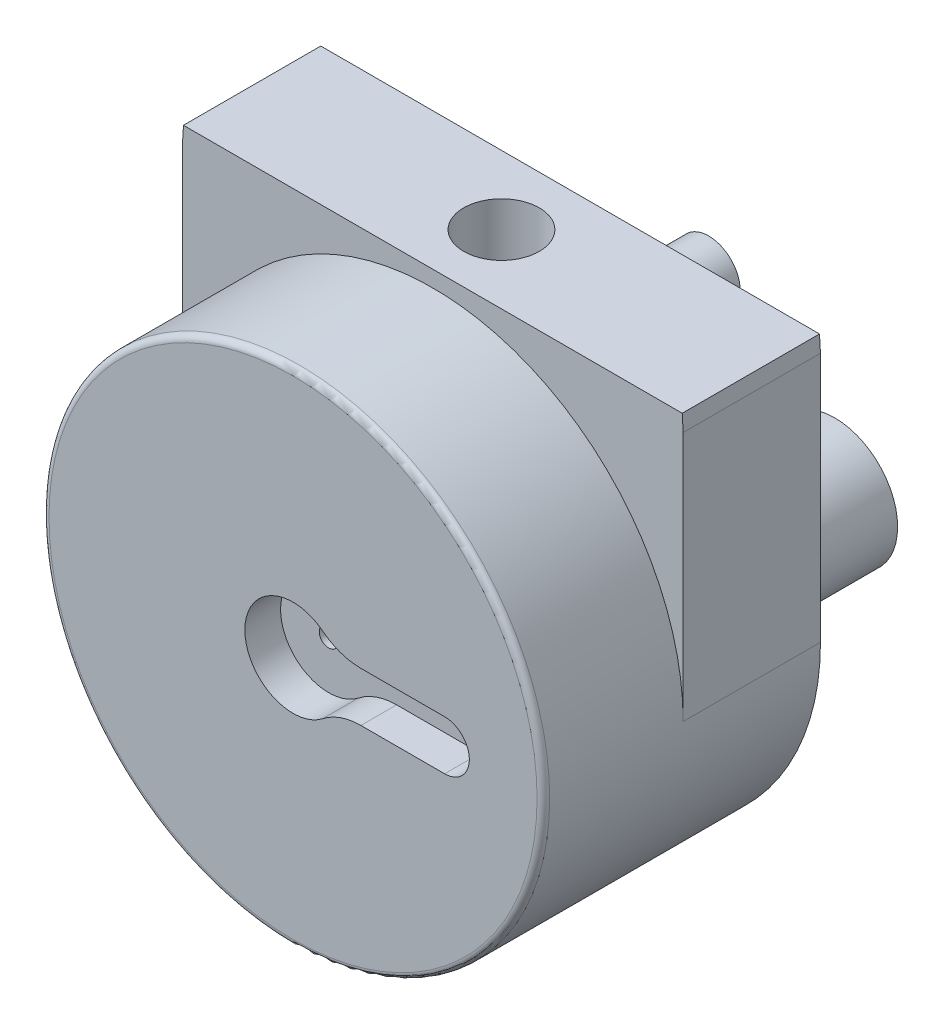
SolidWorks part; units mm, degrees
material "6061 Alloy"
ref_plane "Front Plane" through (0, 0, 0) normal (0, 0, 1) x (1, 0, 0)
ref_plane "Top Plane" through (0, 0, 0) normal (0, 1, 0) x (1, 0, 0)
ref_plane "Right Plane" through (0, 0, 0) normal (1, 0, 0) x (0, 0, -1)
sketch "Sketch1" plane through (0, 0, 0) normal (0, 0, 1) x (1, 0, 0)
  circle A0 centre (0, 0) radius 39.75
  dimension "D1" = 79.5
extrude "Boss-Extrude1" add sketch "Sketch1" along normal blind 44
sketch "Sketch2" plane through (0, 0, 0) normal (0, 1, 0) x (1, 0, 0)
  line L0 (39.75, -44) -> (39.75, 0) construction
  line L1 (-39.75, 0) -> (39.75, 0)
  line L2 (-39.75, 0) -> (-39.75, -21.8)
  line L3 (-39.75, -21.8) -> (39.75, -21.8)
  line L4 (39.75, 0) -> (39.75, -21.8)
  dimension "D1" = 21.8
extrude "Boss-Extrude2" add sketch "Sketch2" along normal through all
sketch "Sketch3" plane through (0, 0, 0) normal (0, 0, -1) x (-1, 0, 0)
  line L0 (0, 0) -> (0, 203.2) construction
  line L1 (-39.75, 39.75) -> (-29.9473, 204.9767)
  line L2 (39.75, 39.75) -> (29.9473, 204.9767)
  line L3 (39.75, 39.75) -> (39.75, 0) construction
  line L4 (-39.75, 39.75) -> (39.75, 39.75) construction
  circle A0 centre (0, 203.2) radius 30
  line M5 (39.75, 39.75) -> (-39.75, 39.75)
  dimension "D1" = 60
  dimension "D2" = 203.2
extrude "Boss-Extrude3" add sketch "Sketch3" against normal up to surface (21.8 mm away) contours L0 A0 L1 M5 | L0 L2 A0 M5 | A0 region at (18.2462, 107.3979, 0) region at (-18.2462, 107.3979, 0) region at (21.2148, 183.2065, 0) up to face at (29.2442, 29.2442, 21.8)
ref_plane "Plane7" through (0, 233.2, 0) normal (0, 1, 0) x (1, 0, 0)
sketch "Sketch5" plane through (0, 0, 21.8) normal (0, 0, 1) x (1, 0, 0)
  line L0 (10.25, 179.4146) -> (10.25, 171.95)
  line L1 (10.25, 171.95) -> (-10.25, 171.95)
  line L2 (-10.25, 171.95) -> (-10.25, 179.4146)
  circle A0 centre (0, 203.2) radius 25.9
  dimension "D1" = 20.5
  dimension "D4" = 51.8
  dimension "D6" = 7.4646
  dimension "D7" = 7.4646
extrude "Cut-Extrude2" cut sketch "Sketch5" against normal up to next contours A0 region at (0, 203.2, 21.8)
extrude "Cut-Extrude3" cut sketch "Sketch5<3>" against normal blind 10.25 contours A0 L2 L1 L0 region at (0, 175.0039, 21.8)
sketch "Sketch5<3>" plane through (0, 0, 21.8) normal (0, 0, 1) x (1, 0, 0) same geometry as "Sketch5"
sketch "Sketch7" plane through (0, 0, 21.8) normal (0, 0, 1) x (1, 0, 0)
  line L0 (-10.25, 171.95) -> (-10.25, 179.4146) construction
  line L1 (10.25, 171.95) -> (-12.25, 171.95)
  line L2 (10.25, 171.95) -> (10.25, 169.95)
  line L3 (10.25, 169.95) -> (-12.25, 169.95)
  line L4 (-12.25, 171.95) -> (-12.25, 169.95)
  line L6 (10.25, 169.95) -> (12.25, 169.95)
  line L7 (10.25, 169.95) -> (10.25, 212.2)
  line L8 (10.25, 212.2) -> (12.25, 212.2)
  line L9 (12.25, 169.95) -> (12.25, 212.2)
  line L10 (-12.25, 212.2) -> (-28.6182, 212.2)
  line L11 (-10.25, 171.95) -> (-12.25, 171.95)
  line L12 (-10.25, 171.95) -> (-10.25, 212.2)
  line L13 (-10.25, 212.2) -> (-12.25, 212.2)
  line L14 (-12.25, 171.95) -> (-12.25, 212.2)
  line L15 (-12.25, 210.2) -> (-29.1719, 210.2)
  line L16 (12.25, 212.2) -> (28.6182, 212.2)
  line L17 (12.25, 210.2) -> (29.1719, 210.2)
  line L18 (0, 203.2) -> (0, 212.2) construction
  line L19 (-10.25, 212.2) -> (10.25, 212.2) construction
  arc A0 (29.9473, 204.9767) -> (-29.9473, 204.9767) centre (0, 203.2) ccw construction
  arc A1 (-28.6182, 212.2) -> (-29.1719, 210.2) centre (0, 203.2) ccw
  arc A2 (29.1719, 210.2) -> (28.6182, 212.2) centre (0, 203.2) ccw
  arc M13 (29.9473, 204.9767) -> (-29.9473, 204.9767) centre (0, 203.2) ccw
  line M15 (10.25, 179.4146) -> (10.25, 171.95)
  line M16 (10.25, 171.95) -> (-10.25, 171.95)
  line M17 (-10.25, 171.95) -> (-10.25, 179.4146)
  arc M18 (-10.25, 179.4146) -> (10.25, 179.4146) centre (0, 203.2) cw
  dimension "D9" = 30
  dimension "D1" = 2
  dimension "D2" = 2
  dimension "D3" = 2
  dimension "D4" = 2
  dimension "D5" = 2
  dimension "D6" = 2
  dimension "D7" = 9
  dimension "D8" = 42.25
extrude "Boss-Extrude5" add sketch "Sketch7" along normal blind 31 contours L15 L14 L10 M18 | L15 L10 M18 M13 | L14 L12 L13 M18 | L14 L1 M17 M18 | L1 L4 L3 L2 M16 | L6 L9 L2 M18 M15 | L9 L8 L7 M18 | L9 L17 L16 M18 | L17 L16 M18 M13 region at (-1, 170.95, 21.8) region at (11.2662, 174.9188, 21.8) region at (-11.2703, 175.9197, 21.8) region at (11.245, 196.0386, 21.8) region at (-11.245, 196.0386, 21.8) region at (18.4394, 211.1912, 21.8) region at (26.7656, 211.2037, 21.8) region at (-18.4394, 211.1912, 21.8) region at (-26.7656, 211.2037, 21.8)
sketch "Sketch8" plane through (0, 212.2, 0) normal (0, 1, 0) x (1, 0, 0)
  line L0 (-29.1719, -23.4904) -> (-12.25, -52.8)
  line L1 (29.1719, -52.8) -> (29.1719, -21.8) construction
  line L2 (12.25, -52.8) -> (29.1719, -23.4904)
  line L4 (-29.1719, -52.8) -> (-29.1719, -21.8) construction
  line L6 (-29.1719, -23.4904) -> (-29.1719, -52.8)
  line L7 (-29.1719, -52.8) -> (-12.25, -52.8)
  line L8 (12.25, -52.8) -> (29.1719, -52.8)
  line L9 (29.1719, -52.8) -> (29.1719, -23.4904)
  line L11 (29.1719, -52.8) -> (29.1719, -21.8) construction
  dimension "D1" = 2
  dimension "D2" = 30
  dimension "D3" = 2
  dimension "D4" = 30
extrude "Cut-Extrude4" cut sketch "Sketch8" against normal blind 10
sketch "Sketch9" plane through (0, 0, 52.8) normal (0, 0, 1) x (1, 0, 0)
  line L0 (-12.25, 169.95) -> (-12.25, 180.3801) construction
  line L1 (-12.25, 169.95) -> (12.25, 169.95)
  line L2 (-12.25, 169.95) -> (-12.25, 212.2)
  line L3 (-12.25, 212.2) -> (12.25, 212.2)
  line L4 (12.25, 169.95) -> (12.25, 212.2)
  line L5 (-12.25, 169.95) -> (-12.25, 210.2) construction
  line L6 (-12.25, 169.95) -> (-7.5, 174.7) construction
  line L7 (-7.5, 174.7) -> (-7.5, 189.7) construction
  line L8 (-7.5, 189.7) -> (-8, 210.2) construction
  line L9 (-8, 210.2) -> (0, 203.2) construction
  line L10 (0, 203.2) -> (8, 210.2) construction
  line L11 (8, 210.2) -> (7.5, 189.7) construction
  line L12 (7.5, 189.7) -> (7.5, 174.7) construction
  line L13 (7.5, 174.7) -> (12.25, 169.95) construction
  circle A0 centre (0, 203.2) radius 7.5
  circle A1 centre (-8, 210.2) radius 0.75
  circle A2 centre (8, 210.2) radius 0.75
  circle A3 centre (7.5, 189.7) radius 0.75
  circle A4 centre (7.5, 174.7) radius 0.75
  circle A5 centre (-7.5, 174.7) radius 0.75
  circle A6 centre (-7.5, 189.7) radius 0.75
  line M25 (12.25, 210.2) -> (12.25, 212.2)
  line M26 (12.25, 212.2) -> (10.25, 212.2)
  line M27 (10.25, 212.2) -> (10.25, 171.95)
  line M28 (10.25, 171.95) -> (-10.25, 171.95)
  line M29 (-10.25, 171.95) -> (-10.25, 212.2)
  line M30 (-10.25, 212.2) -> (-12.25, 212.2)
  line M31 (-12.25, 212.2) -> (-12.25, 210.2)
  line M32 (-12.25, 210.2) -> (-12.25, 169.95)
  line M33 (-12.25, 169.95) -> (12.25, 169.95)
  line M34 (12.25, 169.95) -> (12.25, 210.2)
  dimension "D1" = 1.5
  dimension "D2" = 1.5
  dimension "D3" = 1.5
  dimension "D4" = 1.5
  dimension "D5" = 15
  dimension "D6" = 1.5
  dimension "D7" = 1.5
  dimension "D8" = 45
  dimension "D9" = 15
  dimension "D10" = 6.7175
  dimension "D11" = 20.5
  dimension "D12" = 10.6301
  dimension "D13" = 47.417
  dimension "D14" = 97.628
  dimension "D15" = 47.417
  dimension "D16" = 20.5
  dimension "D17" = 10.6301
  dimension "D18" = 15
extrude "Boss-Extrude6" add sketch "Sketch9" along normal blind 2 contours L3 A6 A5 A4 A3 A2 A1 A0 | M34 M25 M26 M27 M28 M29 M30 M31 M32 M33 region at (-11.7616, 190.075, 52.8) region at (0, 189.0016, 52.8)
sketch "Sketch10" plane through (0, 0, 0) normal (0, 0, -1) x (-1, 0, 0)
  line L0 (-20, 0) -> (20, 0) construction
  line L1 (0, 20) -> (0, -20) construction
  line L2 (0, 0) -> (0, 177.3) construction
  circle A1 centre (-20, 0) radius 10
  circle A2 centre (0, 20) radius 5
  circle A3 centre (20, 0) radius 10
  circle A4 centre (0, -20) radius 5
  circle A5 centre (0, 117.3) radius 5
  circle A6 centre (0, 147.3) radius 10
  circle A7 centre (0, 147.3) radius 5.125
  circle A8 centre (-20, 0) radius 5.125
  circle A9 centre (20, 0) radius 5.125
  circle A10 centre (0, 203.2) radius 25.9 construction
  point P5 (0, 0)
  point P9 (0, 0)
  dimension "D3" = 10
  dimension "D4" = 10
  dimension "D5" = 20
  dimension "D6" = 20
  dimension "D7" = 10
  dimension "D8" = 20
  dimension "D11" = 10.25
  dimension "D12" = 10.25
  dimension "D13" = 10.25
  dimension "D1" = 40
  dimension "D2" = 40
  dimension "D9" = 30
  dimension "D10" = 30
extrude "Boss-Extrude7" add sketch "Sketch10" along normal blind 22
sketch "Sketch11" plane through (0, 0, 0) normal (1, 0, 0) x (0, 0, -1)
  line L1 (-21.8, 161.95) -> (-18.9, 161.95)
  line L2 (-21.8, 204.9767) -> (-21.8, 39.75) construction
  line L3 (-10.9, 153.95) -> (-10.9, 161.95) construction
  line L4 (-10.9, 161.95) -> (-18.9, 161.95) construction
  line L8 (-54.8, 169.95) -> (-21.8, 169.95) construction
  line L18 (-10.9, -39.75) -> (-10.9, 153.95)
  line L22 (-44, -39.75) -> (0, -39.75) construction
  arc A0 (-18.9, 161.95) -> (-10.9, 153.95) centre (-18.9, 153.95) cw
  dimension "D4" = 8
  dimension "D1" = 10.9
  dimension "D2" = 8
  dimension "D3" = 2.9
sweep "Cut-Sweep1" cut path "Sketch11" circular profile diameter 12 parameters "D3"=12
fillet "Fillet3" radius 1 1 edges at (39.75, 0, 44)
sketch "Sketch14" plane through (0, 0, 0) normal (0, 0, -1) x (-1, 0, 0)
  line L0 (-5, -20) -> (5, -20)
  line L1 (-5, -20) -> (-27.8841, -28.3291)
  line L2 (5, -20) -> (27.8841, -28.3291)
  line L3 (-5, -20) -> (0, -18.1801)
  line L4 (0, -18.1801) -> (5, -20)
  circle A0 centre (0, -20) radius 5 construction
  circle A1 centre (0, -20) radius 5 construction
  arc A2 (-39.75, 0) -> (39.75, 0) centre (0, 0) ccw construction
  arc A3 (-27.8841, -28.3291) -> (27.8841, -28.3291) centre (0, 0) ccw
  circle M8 centre (0, -20) radius 5
  arc M18 (-39.75, 0) -> (39.75, 0) centre (0, 0) ccw
  dimension "D1" = 160
  dimension "D2" = 160
extrude "Cut-Extrude6(NEW)" cut sketch "Sketch14" against normal blind 21 and the other way blind 1 from offset 4.9 contours L2 L1 M8 M18 | L0 M8 | L4 L3 L0 region at (0, -19.3934, 0) region at (0, -30.4059, 0) region at (0, -22.1221, 0) offset against normal yes
fillet "Fillet4" radius 1 6 edges at (-13.942, -23.2546, 3.9) (-13.942, -23.2546, 25.9) (-27.8841, -28.3291, 14.9) (0, -39.75, 3.9) (27.8841, -28.3291, 14.9) (0, -39.75, 25.9)
sketch "Sketch20" plane through (0, 0, 21.8) normal (0, 0, 1) x (1, 0, 0)
  circle A1 centre (0, 161.95) radius 7
  dimension "D1" = 14
extrude "Cut-Extrude7(NEW)" cut sketch "Sketch20" against normal through all
sketch "Sketch22" plane through (0, 171.95, 0) normal (0, 1, 0) x (1, 0, 0)
  line L0 (0, -11.55) -> (0, -21.25) construction
  line L1 (10.25, -11.55) -> (-10.25, -11.55) construction
  line L2 (10.25, -11.55) -> (10.25, -52.8) construction
  line L3 (10.25, -21.25) -> (-10.25, -21.25)
  line L4 (10.25, -21.25) -> (10.25, -28.25)
  line L5 (10.25, -28.25) -> (-10.25, -28.25)
  line L6 (-10.25, -21.25) -> (-10.25, -28.25)
  line L7 (-10.25, -52.8) -> (-10.25, -21.8) construction
  dimension "D1" = 9.7
  dimension "D2" = 7
extrude "Cut-Extrude8" cut sketch "Sketch22" against normal blind 6.5
sketch "Sketch23" plane through (0, 0, 44) normal (0, 0, 1) x (1, 0, 0)
  line L0 (24.0717, 0) -> (20.0717, 0) construction
  line L1 (10.7762, 3.725) -> (24.0717, 3.725)
  line L2 (-27.75, -3.875) -> (-27.75, 3.875) construction
  line L7 (24.0717, -3) -> (20.0717, -3)
  line L12 (10.7762, -3.725) -> (24.0717, -3.725)
  line L13 (24.0717, 3) -> (20.0717, 3)
  line L14 (10.7762, -3.925) -> (24.0717, -3.925)
  line L15 (10.7762, 3.925) -> (24.0717, 3.925)
  arc A2 (24.0717, -3.725) -> (24.0717, 3.725) centre (24.0717, 0) ccw
  arc A3 (24.0717, -3) -> (24.0717, 3) centre (24.0717, 0) ccw
  arc A4 (6.4519, 3.725) -> (7.4142, 0.729) centre (0, 0) cw
  arc A5 (4.6007, -5.8597) -> (10.7762, -3.725) centre (10.7762, -13.725) cw
  arc A6 (4.6007, 5.8597) -> (10.7762, 3.725) centre (10.7762, 13.725) ccw
  arc A7 (4.7242, 6.017) -> (4.7242, -6.017) centre (0, 0) ccw
  arc A8 (4.7242, -6.017) -> (10.7762, -3.925) centre (10.7762, -13.725) cw
  arc A9 (24.0717, -3.925) -> (24.0717, 3.925) centre (24.0717, 0) ccw
  arc A10 (4.7242, 6.017) -> (10.7762, 3.925) centre (10.7762, 13.725) ccw
  circle A11 centre (0, 0) radius 1.5
  circle A12 centre (8.95, 0) radius 1.7
  circle A13 centre (20.0717, 0) radius 1.5
  circle A14 centre (24.0717, 0) radius 1.5
  arc A15 (7.4142, -0.729) -> (6.4519, -3.725) centre (0, 0) cw
  point P2 (22.0717, 0)
  point P4 (0, 0)
  point P8 (0, 0)
  point P10 (-27.75, 0)
  point P13 (27.75, 0)
  point P14 (0, 0)
  dimension "D4" = 6
  dimension "D1" = 7.45
  dimension "D5" = 10
  dimension "D6" = 3
  dimension "D7" = 3
  dimension "D8" = 3
  dimension "D2" = 24.0717
  dimension "D3" = 7.75
extrude "Cut-Extrude9(NEW)" cut sketch "Sketch23" against normal blind 5.67 contours A10 A7 A8 L14 A9 L15 A14 A13 A11 A12 region at (7.4478, -4.0961, 44)
sketch "Sketch24" plane through (-41.9606, 2.4895, 0) normal (-0.9982, 0.0592, 0) x (0, 0, 1)
  line L0 (2.0543, 49.6834) -> (2.0543, 53.2013)
  line L1 (15.2985, 60.554) -> (20.2543, 60.554)
  line L2 (20.2543, 60.554) -> (20.2543, 55.7564)
  line L3 (2.2543, 49.8834) -> (2.2543, 53.2013)
  line L4 (15.3, 60.354) -> (20.0543, 60.354)
  line L5 (20.0543, 60.354) -> (20.0543, 55.9564)
  line L6 (20.0543, 55.9564) -> (14.0337, 55.9564)
  line L7 (11.8872, 54.4905) -> (20.0543, 54.4905)
  line L8 (20.0543, 54.4905) -> (20.0543, 49.8834)
  line L9 (20.0543, 49.8834) -> (2.2543, 49.8834)
  line L10 (5.186, 54.4905) -> (9.1649, 54.4905)
  line L11 (7.5517, 55.9564) -> (6.5668, 55.9564)
  line L12 (2.2543, 71.8298) -> (2.2543, 79.7874)
  line L13 (2.2543, 79.7874) -> (5.8143, 79.7874)
  line L14 (5.8143, 79.7874) -> (5.8143, 76.4368)
  line L15 (5.8143, 76.4368) -> (9.1649, 76.4368)
  line L16 (9.1649, 76.4368) -> (9.1649, 79.578)
  line L17 (9.1649, 79.578) -> (12.5154, 79.578)
  line L18 (12.5154, 79.578) -> (12.5154, 76.4368)
  line L19 (12.5154, 76.4368) -> (16.4943, 76.4368)
  line L20 (16.4943, 76.4368) -> (16.4943, 79.9968)
  line L21 (16.4943, 79.9968) -> (20.0543, 79.9968)
  line L22 (20.0543, 79.9968) -> (20.0543, 71.8298)
  line L23 (20.0543, 71.8298) -> (2.2543, 71.8298)
  line L24 (2.2543, 91.0538) -> (2.2543, 94.5712)
  line L25 (8.5333, 101.9432) -> (14.7666, 101.9432)
  line L26 (20.0543, 96.9828) -> (20.0543, 91.0538)
  line L27 (20.0543, 91.0538) -> (2.2543, 91.0538)
  line L28 (5.186, 95.6608) -> (17.1225, 95.6608)
  line L29 (14.4885, 97.3361) -> (7.4372, 97.3361)
  line L30 (2.2543, 113.419) -> (2.2543, 118.1405)
  line L31 (14.1482, 124.3084) -> (15.8202, 124.3084)
  line L32 (20.0543, 118.8309) -> (20.0543, 113.419)
  line L33 (20.0543, 113.419) -> (2.2543, 113.419)
  line L34 (5.186, 118.026) -> (9.1649, 118.026)
  line L35 (11.8872, 118.026) -> (17.1225, 118.026)
  line L36 (15.3785, 119.7013) -> (13.6312, 119.7013)
  line L37 (2.2543, 140.3912) -> (20.0543, 140.3912)
  line L38 (20.0543, 140.3912) -> (20.0543, 135.7841)
  line L39 (20.0543, 135.7841) -> (2.2543, 135.7841)
  line L40 (2.2543, 135.7841) -> (2.2543, 140.3912)
  line L41 (2.2543, 152.0764) -> (2.2543, 155.3942)
  line L42 (15.3, 162.547) -> (20.0543, 162.547)
  line L43 (20.0543, 162.547) -> (20.0543, 158.1493)
  line L44 (20.0543, 158.1493) -> (14.0337, 158.1493)
  line L45 (11.8872, 156.6834) -> (20.0543, 156.6834)
  line L46 (20.0543, 156.6834) -> (20.0543, 152.0764)
  line L47 (20.0543, 152.0764) -> (2.2543, 152.0764)
  line L48 (5.186, 156.6834) -> (9.1649, 156.6834)
  line L49 (7.5517, 158.1493) -> (6.5668, 158.1493)
  line L50 (2.2543, 174.0227) -> (2.2543, 177.5402)
  line L51 (8.5333, 184.9121) -> (14.7666, 184.9121)
  line L52 (20.0543, 179.9517) -> (20.0543, 174.0227)
  line L53 (20.0543, 174.0227) -> (2.2543, 174.0227)
  line L54 (5.186, 178.6298) -> (17.1225, 178.6298)
  line L55 (14.4885, 180.3051) -> (7.4372, 180.3051)
  line L56 (20.2543, 55.7564) -> (14.0337, 55.7564)
  line L57 (12.0921, 54.6905) -> (20.2543, 54.6905)
  line L58 (20.2543, 54.6905) -> (20.2543, 49.6834)
  line L59 (20.2543, 49.6834) -> (2.0543, 49.6834)
  line L60 (5.3915, 54.6905) -> (8.9599, 54.6905)
  line L61 (7.5489, 55.7564) -> (6.5679, 55.7564)
  line L62 (2.0543, 71.6298) -> (2.0543, 79.9874)
  line L63 (2.0543, 79.9874) -> (6.0143, 79.9874)
  line L64 (6.0143, 79.9874) -> (6.0143, 76.6368)
  line L65 (6.0143, 76.6368) -> (8.9649, 76.6368)
  line L66 (8.9649, 76.6368) -> (8.9649, 79.778)
  line L67 (8.9649, 79.778) -> (12.7154, 79.778)
  line L68 (12.7154, 79.778) -> (12.7154, 76.6368)
  line L69 (12.7154, 76.6368) -> (16.2943, 76.6368)
  line L70 (16.2943, 76.6368) -> (16.2943, 80.1968)
  line L71 (16.2943, 80.1968) -> (20.2543, 80.1968)
  line L72 (20.2543, 80.1968) -> (20.2543, 71.6298)
  line L73 (20.2543, 71.6298) -> (2.0543, 71.6298)
  line L74 (8.5326, 102.1432) -> (14.7673, 102.1432)
  line L75 (20.2543, 96.9843) -> (20.2543, 90.8538)
  line L76 (20.2543, 90.8538) -> (2.0543, 90.8538)
  line L77 (2.0543, 90.8538) -> (2.0543, 94.5712)
  line L78 (5.3898, 95.8608) -> (16.9188, 95.8608)
  line L79 (14.4893, 97.1361) -> (7.4348, 97.1361)
  line L80 (14.1479, 124.5084) -> (15.8203, 124.5084)
  line L81 (20.2543, 118.8321) -> (20.2543, 113.219)
  line L82 (20.2543, 113.219) -> (2.0543, 113.219)
  line L83 (2.0543, 113.219) -> (2.0543, 118.1417)
  line L84 (5.3903, 118.226) -> (8.96, 118.226)
  line L85 (12.0964, 118.226) -> (16.9125, 118.226)
  line L86 (15.3808, 119.5013) -> (13.6314, 119.5013)
  line L87 (2.0543, 140.5912) -> (20.2543, 140.5912)
  line L88 (20.2543, 140.5912) -> (20.2543, 135.5841)
  line L89 (20.2543, 135.5841) -> (2.0543, 135.5841)
  line L90 (2.0543, 135.5841) -> (2.0543, 140.5912)
  line L95 (15.2985, 162.747) -> (20.2543, 162.747)
  line L96 (20.2543, 162.747) -> (20.2543, 157.9493)
  line L97 (20.2543, 157.9493) -> (14.0337, 157.9493)
  line L98 (12.0921, 156.8834) -> (20.2543, 156.8834)
  line L99 (20.2543, 156.8834) -> (20.2543, 151.8764)
  line L100 (20.2543, 151.8764) -> (2.0543, 151.8764)
  line L101 (2.0543, 151.8764) -> (2.0543, 155.3942)
  line L102 (5.3915, 156.8834) -> (8.9599, 156.8834)
  line L103 (7.5489, 157.9493) -> (6.5679, 157.9493)
  line L104 (8.5326, 185.1121) -> (14.7673, 185.1121)
  line L105 (20.2543, 179.9533) -> (20.2543, 173.8227)
  line L106 (20.2543, 173.8227) -> (2.0543, 173.8227)
  line L107 (2.0543, 173.8227) -> (2.0543, 177.5402)
  line L108 (5.3898, 178.8298) -> (16.9188, 178.8298)
  line L109 (14.4893, 180.1051) -> (7.4348, 180.1051)
  spline S0 degree 3 poles (2.2543, 53.2013) (2.2524, 53.7107) (2.2609, 54.4405) (2.2883, 55.3686) (2.3127, 55.9644) (2.3488, 56.4935) (2.3905, 56.955) (2.4378, 57.3495) (2.4964, 57.6866) (2.5727, 57.9837) (2.6729, 58.2579) (2.7922, 58.5203) (2.9412, 58.7678) (3.1161, 58.9986) (3.3084, 59.2211) (3.5318, 59.4236) (3.7758, 59.6184) (4.0541, 59.7945) (4.3701, 59.9435) (4.7229, 60.0713) (5.1139, 60.175) (5.5427, 60.2553) (6.1889, 60.3377) (6.6955, 60.3492) (7.0446, 60.354) knots 0 0 0 0 0.148881 0.213303 0.271377 0.323138 0.368276 0.406827 0.439217 0.468212 0.496346 0.524443 0.552325 0.580569 0.609028 0.638128 0.668547 0.700209 0.734143 0.770448 0.80973 0.852244 0.897872 1 1 1 1
  spline S1 degree 3 poles (7.0446, 60.354) (7.3581, 60.3592) (7.8079, 60.338) (8.3791, 60.289) (8.7445, 60.228) (9.0689, 60.1585) (9.3531, 60.0723) (9.5929, 59.964) (9.7974, 59.8411) (9.9702, 59.6911) (10.1214, 59.5118) (10.255, 59.3015) (10.3706, 59.0599) (10.4622, 58.7862) (10.5789, 58.3658) (10.6225, 58.0268) (10.6438, 57.792) knots 0 0 0 0 0.183844 0.264214 0.336185 0.401092 0.458783 0.510057 0.555172 0.598283 0.643683 0.692329 0.744143 0.800414 0.861431 1 1 1 1
  spline S2 degree 3 poles (10.6438, 57.792) (10.702, 58.0046) (10.7842, 58.3129) (10.9286, 58.6959) (11.0437, 58.9407) (11.1615, 59.1589) (11.2844, 59.3507) (11.4197, 59.5123) (11.6042, 59.6868) (11.8391, 59.8592) (12.1101, 60.033) (12.3707, 60.1602) (12.5927, 60.2331) (12.7952, 60.2659) (12.9969, 60.2928) (13.2526, 60.3098) (13.5602, 60.3264) (13.9202, 60.3387) (14.5058, 60.3539) (14.9717, 60.3492) (15.3, 60.354) knots 0 0 0 0 0.11021 0.159198 0.204304 0.245276 0.283065 0.317885 0.350264 0.409778 0.463156 0.510931 0.554366 0.579275 0.613344 0.655979 0.70728 0.767268 0.835956 1 1 1 1
  spline S3 degree 3 poles (14.0337, 55.9564) (13.8145, 55.9546) (13.503, 55.9546) (13.1117, 55.9259) (12.8692, 55.9007) (12.6605, 55.8685) (12.4855, 55.8318) (12.346, 55.7827) (12.2352, 55.7264) (12.1457, 55.6532) (12.0792, 55.5534) (12.0146, 55.4369) (11.9725, 55.2912) (11.9315, 55.1259) (11.8979, 54.8557) (11.8876, 54.6414) (11.8872, 54.4905) knots 0 0 0 0 0.208735 0.296167 0.373443 0.440695 0.497113 0.543415 0.581035 0.614932 0.652106 0.694368 0.741317 0.795712 0.856499 1 1 1 1
  spline S4 degree 3 poles (9.1649, 54.4905) (9.1598, 54.7207) (9.1563, 55.0454) (9.0543, 55.4227) (8.9778, 55.6032) (8.8784, 55.7115) (8.7778, 55.7812) (8.6441, 55.8339) (8.4829, 55.8793) (8.2922, 55.914) (7.9794, 55.9517) (7.7283, 55.9514) (7.5517, 55.9564) knots 0 0 0 0 0.26299 0.361623 0.442867 0.481356 0.526611 0.580322 0.643299 0.716254 0.799641 1 1 1 1
  spline S5 degree 3 poles (6.5668, 55.9564) (6.3319, 55.954) (6.0027, 55.9378) (5.6283, 55.7976) (5.4387, 55.6513) (5.3228, 55.4405) (5.199, 55.0583) (5.1906, 54.7253) (5.186, 54.4905) knots 0 0 0 0 0.296724 0.405999 0.497474 0.590179 0.702697 1 1 1 1
  spline S6 degree 3 poles (2.2543, 94.5712) (2.2491, 95.0927) (2.265, 95.841) (2.2922, 96.7934) (2.33, 97.4041) (2.3703, 97.9455) (2.4223, 98.4181) (2.4818, 98.8226) (2.5754, 99.2617) (2.7252, 99.7315) (2.9502, 100.2311) (3.2277, 100.6593) (3.5615, 101.0092) (3.9246, 101.2929) (4.3099, 101.5197) (4.7148, 101.6881) (5.0766, 101.7807) (5.3993, 101.8254) (5.6937, 101.8588) (6.0399, 101.8825) (6.4379, 101.9069) (6.8875, 101.921) (7.5919, 101.9412) (8.1462, 101.9404) (8.5333, 101.9432) knots 0 0 0 0 0.131285 0.188439 0.239882 0.285335 0.325123 0.359574 0.38823 0.438082 0.483425 0.52585 0.56587 0.6046 0.641526 0.678093 0.71466 0.735206 0.760074 0.789266 0.822551 0.860474 0.902505 1 1 1 1
  spline S7 degree 3 poles (14.7666, 101.9432) (15.133, 101.9409) (15.6581, 101.942) (16.3242, 101.9112) (16.75, 101.8915) (17.1252, 101.858) (17.452, 101.8209) (17.728, 101.7717) (18.0273, 101.7045) (18.3499, 101.5927) (18.69, 101.4099) (18.9916, 101.1908) (19.2402, 100.9191) (19.454, 100.6164) (19.6325, 100.2789) (19.7712, 99.9065) (19.8617, 99.5716) (19.9157, 99.2781) (19.9572, 99.0288) (19.9829, 98.752) (20.0113, 98.449) (20.0284, 98.1204) (20.0546, 97.6288) (20.0501, 97.2466) (20.0543, 96.9828) knots 0 0 0 0 0.124489 0.178253 0.226484 0.269248 0.306193 0.33817 0.36441 0.410339 0.453597 0.495164 0.536313 0.578044 0.620801 0.665593 0.712772 0.73842 0.766924 0.79859 0.832802 0.870285 0.910339 1 1 1 1
  spline S8 degree 3 poles (17.1225, 95.6608) (17.1216, 95.8332) (17.114, 96.0806) (17.0668, 96.3883) (17.0282, 96.5807) (16.9661, 96.7425) (16.9013, 96.8829) (16.8149, 96.9922) (16.7121, 97.0788) (16.5792, 97.1414) (16.4091, 97.1918) (16.1966, 97.2359) (15.9401, 97.2752) (15.6396, 97.3033) (15.1509, 97.3292) (14.7624, 97.3383) (14.4885, 97.3361) knots 0 0 0 0 0.13711 0.195797 0.247292 0.292516 0.333197 0.369593 0.402205 0.439011 0.485318 0.542921 0.611291 0.691374 0.782488 1 1 1 1
  spline S9 degree 3 poles (7.4372, 97.3361) (7.2506, 97.3407) (6.9845, 97.3318) (6.6475, 97.3241) (6.4358, 97.3151) (6.2517, 97.3001) (6.0949, 97.2908) (5.9668, 97.2688) (5.8339, 97.2467) (5.6966, 97.1938) (5.5516, 97.1104) (5.4354, 96.9895) (5.3332, 96.8397) (5.2685, 96.6339) (5.1899, 96.2406) (5.1913, 95.9043) (5.186, 95.6608) knots 0 0 0 0 0.161837 0.230941 0.292514 0.345641 0.39122 0.428559 0.458438 0.507835 0.555384 0.602223 0.652089 0.71135 0.787624 1 1 1 1
  spline S10 degree 3 poles (2.2543, 118.1405) (2.2583, 118.4906) (2.2613, 118.9994) (2.2964, 119.655) (2.3369, 120.0955) (2.3816, 120.5027) (2.4357, 120.8765) (2.5045, 121.216) (2.5827, 121.5259) (2.6782, 121.8122) (2.7961, 122.0801) (2.9347, 122.3336) (3.092, 122.5744) (3.2731, 122.8008) (3.4757, 123.0131) (3.7005, 123.2107) (3.9473, 123.3958) (4.2245, 123.5657) (4.5415, 123.7088) (4.8982, 123.8287) (5.2916, 123.9299) (5.7253, 124.0033) (6.3781, 124.0791) (6.8902, 124.1029) (7.2442, 124.099) knots 0 0 0 0 0.114375 0.166108 0.21439 0.258844 0.299904 0.337701 0.371916 0.404248 0.43615 0.467396 0.498519 0.529953 0.561953 0.594259 0.627603 0.66261 0.70023 0.740899 0.785396 0.832777 0.884431 1 1 1 1
  spline S11 degree 3 poles (7.2442, 124.099) (7.4812, 124.1027) (7.8229, 124.0851) (8.2564, 124.0306) (8.5398, 123.9816) (8.7925, 123.9072) (9.0192, 123.8256) (9.2154, 123.7222) (9.3876, 123.6029) (9.5377, 123.4558) (9.6806, 123.2859) (9.8049, 123.08) (9.9276, 122.8491) (10.0427, 122.5875) (10.1786, 122.1774) (10.2698, 121.8534) (10.3166, 121.6253) knots 0 0 0 0 0.159635 0.229972 0.294227 0.35305 0.407212 0.456169 0.502024 0.547743 0.597307 0.65111 0.709269 0.77341 0.843331 1 1 1 1
  spline S12 degree 3 poles (10.3166, 121.6253) (10.3725, 121.8692) (10.4727, 122.2201) (10.6533, 122.6535) (10.7959, 122.9376) (10.958, 123.1872) (11.1304, 123.4091) (11.3214, 123.5978) (11.5327, 123.7547) (11.7658, 123.8857) (12.0225, 124.0017) (12.3084, 124.0944) (12.6211, 124.173) (12.962, 124.2353) (13.4737, 124.2916) (13.873, 124.3075) (14.1482, 124.3084) knots 0 0 0 0 0.144043 0.209309 0.269932 0.32668 0.380292 0.431325 0.480651 0.531247 0.584899 0.64245 0.703941 0.770287 0.841669 1 1 1 1
  spline S13 degree 3 poles (15.8202, 124.3084) (16.105, 124.3082) (16.5181, 124.2978) (17.0491, 124.2528) (17.4031, 124.2086) (17.7275, 124.1492) (18.0218, 124.0783) (18.288, 123.994) (18.5975, 123.8656) (18.9388, 123.6678) (19.2809, 123.3602) (19.5501, 122.9886) (19.7172, 122.6267) (19.8132, 122.2867) (19.8782, 121.9685) (19.9313, 121.5913) (19.9769, 121.1537) (20.0114, 120.6582) (20.0492, 119.8774) (20.0492, 119.2617) (20.0543, 118.8309) knots 0 0 0 0 0.102269 0.148253 0.191288 0.230306 0.266588 0.299901 0.330446 0.386794 0.440584 0.494395 0.550463 0.582684 0.621084 0.666995 0.719365 0.779044 0.845298 1 1 1 1
  spline S14 degree 2 poles (9.1649, 118.026) (9.158, 118.2812) (9.155, 118.5365) knots 0 0 0 1 1 1
  spline S15 degree 3 poles (9.155, 118.5365) (9.1579, 118.7431) (9.133, 119.0337) (8.9824, 119.3569) (8.8469, 119.4881) (8.7043, 119.5504) (8.5607, 119.5934) (8.3767, 119.6219) (8.1545, 119.6526) (7.8934, 119.6739) (7.467, 119.6971) (7.1275, 119.7009) (6.8875, 119.7013) knots 0 0 0 0 0.207117 0.283923 0.350831 0.389245 0.438074 0.499907 0.574465 0.661754 0.760817 1 1 1 1
  spline S16 degree 3 poles (6.8875, 119.7013) (6.6489, 119.704) (6.3205, 119.6872) (5.9256, 119.6186) (5.7173, 119.5414) (5.558, 119.4472) (5.4338, 119.3409) (5.3385, 119.2221) (5.2761, 119.0788) (5.2385, 118.899) (5.197, 118.5455) (5.1898, 118.2464) (5.186, 118.026) knots 0 0 0 0 0.246774 0.340005 0.413619 0.475395 0.530632 0.582131 0.631661 0.690822 0.771636 1 1 1 1
  spline S17 degree 3 poles (17.1225, 118.026) (17.115, 118.1897) (17.1052, 118.4245) (17.063, 118.7183) (17.0287, 118.9036) (16.9825, 119.0642) (16.9314, 119.2017) (16.8737, 119.3159) (16.8016, 119.4067) (16.7101, 119.4781) (16.5984, 119.541) (16.4578, 119.5872) (16.2932, 119.6309) (16.1013, 119.6617) (15.7938, 119.6926) (15.55, 119.7054) (15.3785, 119.7013) knots 0 0 0 0 0.168584 0.241049 0.305039 0.362178 0.412572 0.455707 0.493181 0.530655 0.574326 0.624331 0.682257 0.749354 0.823771 1 1 1 1
  spline S18 degree 3 poles (13.6312, 119.7013) (13.4513, 119.7011) (13.1938, 119.6986) (12.873, 119.6632) (12.674, 119.6414) (12.5072, 119.6005) (12.3675, 119.5572) (12.2581, 119.5018) (12.172, 119.437) (12.1095, 119.3498) (12.059, 119.2406) (12.0133, 119.1045) (11.9755, 118.9411) (11.9432, 118.751) (11.9067, 118.4436) (11.8935, 118.1986) (11.8872, 118.026) knots 0 0 0 0 0.182344 0.260037 0.326886 0.384748 0.433642 0.474638 0.508444 0.541576 0.582078 0.629925 0.686713 0.751712 0.825136 1 1 1 1
  spline S19 degree 3 poles (2.2543, 155.3942) (2.2524, 155.9036) (2.2609, 156.6335) (2.2883, 157.5616) (2.3127, 158.1573) (2.3488, 158.6864) (2.3905, 159.148) (2.4378, 159.5424) (2.4964, 159.8795) (2.5727, 160.1766) (2.6729, 160.4508) (2.7922, 160.7132) (2.9412, 160.9607) (3.1161, 161.1916) (3.3084, 161.414) (3.5318, 161.6165) (3.7758, 161.8114) (4.0541, 161.9875) (4.3701, 162.1364) (4.7229, 162.2643) (5.1139, 162.368) (5.5427, 162.4483) (6.1889, 162.5306) (6.6955, 162.5421) (7.0446, 162.547) knots 0 0 0 0 0.148881 0.213303 0.271377 0.323138 0.368276 0.406827 0.439217 0.468212 0.496346 0.524443 0.552325 0.580569 0.609028 0.638128 0.668547 0.700209 0.734143 0.770448 0.80973 0.852244 0.897872 1 1 1 1
  spline S20 degree 3 poles (7.0446, 162.547) (7.3581, 162.5522) (7.8079, 162.5309) (8.3791, 162.4819) (8.7445, 162.421) (9.0689, 162.3514) (9.3531, 162.2653) (9.5929, 162.157) (9.7974, 162.034) (9.9702, 161.884) (10.1214, 161.7048) (10.255, 161.4944) (10.3706, 161.2528) (10.4622, 160.9792) (10.5789, 160.5588) (10.6225, 160.2197) (10.6438, 159.9849) knots 0 0 0 0 0.183844 0.264214 0.336185 0.401092 0.458783 0.510057 0.555172 0.598283 0.643683 0.692329 0.744143 0.800414 0.861431 1 1 1 1
  spline S21 degree 3 poles (10.6438, 159.9849) (10.702, 160.1975) (10.7842, 160.5059) (10.9286, 160.8889) (11.0437, 161.1337) (11.1615, 161.3519) (11.2844, 161.5436) (11.4197, 161.7052) (11.6042, 161.8797) (11.8391, 162.0522) (12.1101, 162.2259) (12.3707, 162.3531) (12.5927, 162.426) (12.7952, 162.4589) (12.9969, 162.4858) (13.2526, 162.5028) (13.5602, 162.5194) (13.9202, 162.5316) (14.5058, 162.5468) (14.9717, 162.5421) (15.3, 162.547) knots 0 0 0 0 0.11021 0.159198 0.204304 0.245276 0.283065 0.317885 0.350264 0.409778 0.463156 0.510931 0.554366 0.579275 0.613344 0.655979 0.70728 0.767268 0.835956 1 1 1 1
  spline S22 degree 3 poles (14.0337, 158.1493) (13.8145, 158.1475) (13.503, 158.1475) (13.1117, 158.1189) (12.8692, 158.0936) (12.6605, 158.0615) (12.4855, 158.0248) (12.346, 157.9756) (12.2352, 157.9194) (12.1457, 157.8461) (12.0792, 157.7464) (12.0146, 157.6299) (11.9725, 157.4842) (11.9315, 157.3189) (11.8979, 157.0486) (11.8876, 156.8343) (11.8872, 156.6834) knots 0 0 0 0 0.208735 0.296167 0.373443 0.440695 0.497113 0.543415 0.581035 0.614932 0.652106 0.694368 0.741317 0.795712 0.856499 1 1 1 1
  spline S23 degree 3 poles (9.1649, 156.6834) (9.1598, 156.9136) (9.1563, 157.2383) (9.0543, 157.6156) (8.9778, 157.7961) (8.8784, 157.9045) (8.7778, 157.9741) (8.6441, 158.0268) (8.4829, 158.0723) (8.2922, 158.1069) (7.9794, 158.1447) (7.7283, 158.1444) (7.5517, 158.1493) knots 0 0 0 0 0.26299 0.361623 0.442867 0.481356 0.526611 0.580322 0.643299 0.716254 0.799641 1 1 1 1
  spline S24 degree 3 poles (6.5668, 158.1493) (6.3319, 158.1469) (6.0027, 158.1307) (5.6283, 157.9905) (5.4387, 157.8442) (5.3228, 157.6334) (5.199, 157.2513) (5.1906, 156.9183) (5.186, 156.6834) knots 0 0 0 0 0.296724 0.405999 0.497474 0.590179 0.702697 1 1 1 1
  spline S25 degree 3 poles (2.2543, 177.5402) (2.2491, 178.0617) (2.265, 178.8099) (2.2922, 179.7623) (2.33, 180.373) (2.3703, 180.9145) (2.4223, 181.3871) (2.4818, 181.7915) (2.5754, 182.2306) (2.7252, 182.7005) (2.9502, 183.2001) (3.2277, 183.6283) (3.5615, 183.9782) (3.9246, 184.2619) (4.3099, 184.4886) (4.7148, 184.657) (5.0766, 184.7496) (5.3993, 184.7943) (5.6937, 184.8277) (6.0399, 184.8515) (6.4379, 184.8758) (6.8875, 184.8899) (7.5919, 184.9102) (8.1462, 184.9093) (8.5333, 184.9121) knots 0 0 0 0 0.131285 0.188439 0.239882 0.285335 0.325123 0.359574 0.38823 0.438082 0.483425 0.52585 0.56587 0.6046 0.641526 0.678093 0.71466 0.735206 0.760074 0.789266 0.822551 0.860474 0.902505 1 1 1 1
  spline S26 degree 3 poles (14.7666, 184.9121) (15.133, 184.9098) (15.6581, 184.911) (16.3242, 184.8802) (16.75, 184.8605) (17.1252, 184.8269) (17.452, 184.7898) (17.728, 184.7407) (18.0273, 184.6735) (18.3499, 184.5617) (18.69, 184.3789) (18.9916, 184.1597) (19.2402, 183.8881) (19.454, 183.5854) (19.6325, 183.2478) (19.7712, 182.8754) (19.8617, 182.5405) (19.9157, 182.2471) (19.9572, 181.9977) (19.9829, 181.7209) (20.0113, 181.418) (20.0284, 181.0893) (20.0546, 180.5978) (20.0501, 180.2155) (20.0543, 179.9517) knots 0 0 0 0 0.124489 0.178253 0.226484 0.269248 0.306193 0.33817 0.36441 0.410339 0.453597 0.495164 0.536313 0.578044 0.620801 0.665593 0.712772 0.73842 0.766924 0.79859 0.832802 0.870285 0.910339 1 1 1 1
  spline S27 degree 3 poles (17.1225, 178.6298) (17.1216, 178.8021) (17.114, 179.0495) (17.0668, 179.3572) (17.0282, 179.5497) (16.9661, 179.7115) (16.9013, 179.8519) (16.8149, 179.9612) (16.7121, 180.0477) (16.5792, 180.1103) (16.4091, 180.1607) (16.1966, 180.2048) (15.9401, 180.2442) (15.6396, 180.2723) (15.1509, 180.2981) (14.7624, 180.3073) (14.4885, 180.3051) knots 0 0 0 0 0.13711 0.195797 0.247292 0.292516 0.333197 0.369593 0.402205 0.439011 0.485318 0.542921 0.611291 0.691374 0.782488 1 1 1 1
  spline S28 degree 3 poles (7.4372, 180.3051) (7.2506, 180.3096) (6.9845, 180.3007) (6.6475, 180.293) (6.4358, 180.2841) (6.2517, 180.2691) (6.0949, 180.2597) (5.9668, 180.2377) (5.8339, 180.2156) (5.6966, 180.1627) (5.5516, 180.0794) (5.4354, 179.9585) (5.3332, 179.8086) (5.2685, 179.6029) (5.1899, 179.2096) (5.1913, 178.8733) (5.186, 178.6298) knots 0 0 0 0 0.161837 0.230941 0.292514 0.345641 0.39122 0.428559 0.458438 0.507835 0.555384 0.602223 0.652089 0.71135 0.787624 1 1 1 1
  spline S29 degree 1 poles (2.0543, 53.2013) (7.0415, 60.554) knots 0 0 1 1 construction
  spline S30 degree 1 poles (7.0415, 60.554) (10.7031, 58.6618) knots 0 0 1 1 construction
  spline S31 degree 1 poles (10.7031, 58.6618) (15.2985, 60.554) knots 0 0 1 1 construction
  spline S32 degree 1 poles (14.0337, 55.7564) (12.0921, 54.6905) knots 0 0 1 1 construction
  spline S33 degree 3 poles (2.0543, 53.2013) (2.0512, 54.0598) (2.0724, 55.3508) (2.1791, 57.0578) (2.4067, 58.4016) (3.2334, 59.5508) (4.4263, 60.2569) (5.7419, 60.5158) (6.6066, 60.548) (7.0415, 60.554) knots 0.00007 0.00007 0.00007 0.00007 0.250046 0.375034 0.500022 0.62501 0.749998 0.874985 0.999973 0.999973 0.999973 0.999973
  spline S34 degree 3 poles (7.0415, 60.554) (7.4049, 60.56) (8.1306, 60.5271) (9.0394, 60.4018) (9.7715, 60.1289) (10.2519, 59.7203) (10.5443, 59.2007) (10.6548, 58.8441) (10.7031, 58.6618) knots 0.000053 0.000053 0.000053 0.000053 0.209433 0.418812 0.523502 0.628192 0.732882 0.837572 0.837572 0.837572 0.837572
  spline S35 degree 3 poles (10.7031, 58.6618) (10.7848, 58.8729) (10.9659, 59.2789) (11.4411, 59.8503) (11.911, 60.1538) (12.3286, 60.3661) (12.8128, 60.4905) (13.3509, 60.5154) (14.2222, 60.5544) (14.8668, 60.5477) (15.2985, 60.554) knots 0.139052 0.139052 0.139052 0.139052 0.246701 0.35435 0.461999 0.515824 0.569649 0.677298 0.784947 1.000245 1.000245 1.000245 1.000245
  spline S36 degree 3 poles (14.0337, 55.7564) (13.7923, 55.7544) (13.4274, 55.7535) (12.953, 55.7101) (12.6034, 55.6628) (12.3495, 55.5749) (12.2704, 55.4858) (12.1227, 55.22) (12.1024, 54.9129) (12.0921, 54.6905) knots 0.000524 0.000524 0.000524 0.000524 0.233788 0.35042 0.467053 0.583685 0.642001 0.700317 0.933582 0.933582 0.933582 0.933582
  spline S37 degree 1 poles (6.5679, 55.7564) (5.3915, 54.6905) knots 0 0 1 1 construction
  spline S38 degree 1 poles (8.9599, 54.6905) (7.5489, 55.7564) knots 0 0 1 1 construction
  spline S39 degree 3 poles (6.5679, 55.7564) (6.3975, 55.7546) (6.0456, 55.7394) (5.6688, 55.6115) (5.5329, 55.4211) (5.4201, 55.1136) (5.3981, 54.8574) (5.3915, 54.6905) knots 0.000432 0.000432 0.000432 0.000432 0.228515 0.456599 0.57064 0.684682 0.912765 0.912765 0.912765 0.912765
  spline S40 degree 3 poles (8.9599, 54.6905) (8.9538, 54.8781) (8.9301, 55.1667) (8.8086, 55.5118) (8.6928, 55.6102) (8.4223, 55.6918) (8.0514, 55.7487) (7.7465, 55.7509) (7.5489, 55.7564) knots 0.07818 0.07818 0.07818 0.07818 0.308374 0.423471 0.538568 0.653665 0.768762 0.998955 0.998955 0.998955 0.998955
  spline S41 degree 1 poles (2.0543, 94.5712) (8.5326, 102.1432) knots 0 0 1 1 construction
  spline S42 degree 1 poles (14.7673, 102.1432) (20.2543, 96.9843) knots 0 0 1 1 construction
  spline S43 degree 3 poles (2.0543, 94.5712) (2.0493, 95.07) (2.0653, 96.0678) (2.1297, 97.562) (2.2671, 99.0681) (2.7867, 100.5786) (3.7831, 101.5118) (4.7628, 101.9385) (5.8003, 102.0891) (7.0375, 102.132) (8.0348, 102.1396) (8.5326, 102.1432) knots 0.000165 0.000165 0.000165 0.000165 0.125152 0.250139 0.375126 0.500113 0.6251 0.687594 0.750087 0.875074 1.000061 1.000061 1.000061 1.000061
  spline S44 degree 3 poles (14.7673, 102.1432) (15.137, 102.1408) (15.8766, 102.1389) (16.9856, 102.0817) (18.1245, 101.9562) (19.227, 101.3717) (19.8849, 100.3427) (20.2515, 98.8386) (20.2425, 97.7296) (20.2543, 96.9843) knots -0.000072 -0.000072 -0.000072 -0.000072 0.124959 0.249991 0.375022 0.500053 0.625084 0.750116 1.000178 1.000178 1.000178 1.000178
  spline S45 degree 1 poles (7.4348, 97.1361) (5.3898, 95.8608) knots 0 0 1 1 construction
  spline S46 degree 1 poles (16.9188, 95.8608) (14.4893, 97.1361) knots 0 0 1 1 construction
  spline S47 degree 3 poles (7.4348, 97.1361) (7.1675, 97.1427) (6.769, 97.1319) (6.2273, 97.1009) (5.733, 97.0549) (5.4189, 96.6894) (5.3951, 96.1151) (5.3898, 95.8608) knots -0.000705 -0.000705 -0.000705 -0.000705 0.234687 0.352383 0.47008 0.705472 0.940865 0.940865 0.940865 0.940865
  spline S48 degree 3 poles (16.9188, 95.8608) (16.9092, 96.1326) (16.8446, 96.6066) (16.629, 96.939) (16.233, 97.0287) (15.8068, 97.0926) (15.226, 97.1269) (14.7831, 97.1385) (14.4893, 97.1361) knots 0.054835 0.054835 0.054835 0.054835 0.29118 0.409352 0.527524 0.645697 0.763869 1.000214 1.000214 1.000214 1.000214
  spline S49 degree 1 poles (2.0543, 118.1417) (7.2437, 124.299) knots 0 0 1 1 construction
  spline S50 degree 1 poles (7.2437, 124.299) (10.3246, 122.3682) knots 0 0 1 1 construction
  spline S51 degree 1 poles (10.3246, 122.3682) (14.1479, 124.5084) knots 0 0 1 1 construction
  spline S52 degree 1 poles (15.8203, 124.5084) (20.2543, 118.8321) knots 0 0 1 1 construction
  spline S53 degree 3 poles (2.0543, 118.1417) (2.0632, 118.9137) (2.0974, 120.0626) (2.3457, 121.6217) (2.8822, 122.7419) (3.7686, 123.6004) (4.9075, 124.0884) (6.0747, 124.262) (6.8537, 124.3032) (7.2437, 124.299) knots -0.000126 -0.000126 -0.000126 -0.000126 0.249834 0.374814 0.499795 0.624775 0.749755 0.874735 0.999715 0.999715 0.999715 0.999715
  spline S54 degree 3 poles (7.2437, 124.299) (7.5656, 124.3039) (8.2038, 124.2586) (9.02, 124.0953) (9.6262, 123.6903) (10.0456, 123.1267) (10.2259, 122.6801) (10.3246, 122.3682) knots 0.000583 0.000583 0.000583 0.000583 0.210772 0.42096 0.526055 0.631149 0.841338 0.841338 0.841338 0.841338
  spline S55 degree 3 poles (10.3246, 122.3682) (10.4595, 122.7398) (10.7127, 123.2738) (11.3078, 123.8742) (12.0318, 124.2568) (12.9993, 124.4722) (13.7635, 124.5072) (14.1479, 124.5084) knots 0.134807 0.134807 0.134807 0.134807 0.35112 0.459277 0.567433 0.783746 1.00006 1.00006 1.00006 1.00006
  spline S56 degree 3 poles (15.8203, 124.5084) (16.174, 124.5081) (16.8802, 124.4849) (17.9423, 124.3435) (19.0078, 123.9538) (19.8196, 123.0815) (20.1061, 121.9796) (20.1994, 120.9339) (20.2499, 119.8764) (20.2502, 119.181) (20.2543, 118.8321) knots -0.000009 -0.000009 -0.000009 -0.000009 0.125009 0.250028 0.375047 0.500065 0.625084 0.750102 0.875121 1.00014 1.00014 1.00014 1.00014
  spline S57 degree 1 poles (6.8862, 119.5013) (5.3903, 118.226) knots 0 0 1 1 construction
  spline S58 degree 1 poles (8.96, 118.226) (8.955, 118.5367) knots 0 0 1 1 construction
  spline S59 degree 1 poles (8.955, 118.5367) (6.8862, 119.5013) knots 0 0 1 1 construction
  spline S60 degree 3 poles (6.8862, 119.5013) (6.6712, 119.5037) (6.228, 119.4872) (5.745, 119.3613) (5.4948, 119.1284) (5.415, 118.8012) (5.3962, 118.4413) (5.3903, 118.226) knots -0.000333 -0.000333 -0.000333 -0.000333 0.232017 0.464368 0.580543 0.696718 0.929068 0.929068 0.929068 0.929068
  spline S61 degree 2 poles (8.96, 118.226) (8.9568, 118.3813) (8.955, 118.5367) knots 0.399977 0.399977 0.399977 1.004997 1.004997 1.004997
  spline S62 degree 3 poles (8.955, 118.5367) (8.958, 118.7535) (8.8995, 119.1532) (8.7077, 119.359) (8.3642, 119.4257) (8, 119.4677) (7.5087, 119.4958) (7.1345, 119.5009) (6.8862, 119.5013) knots -0.000852 -0.000852 -0.000852 -0.000852 0.249441 0.374588 0.499734 0.624881 0.750027 1.000321 1.000321 1.000321 1.000321
  spline S63 degree 1 poles (13.6314, 119.5013) (12.0964, 118.226) knots 0 0 1 1 construction
  spline S64 degree 1 poles (16.9125, 118.226) (15.3808, 119.5013) knots 0 0 1 1 construction
  spline S65 degree 3 poles (13.6314, 119.5013) (13.4092, 119.501) (13.0683, 119.4855) (12.6461, 119.44) (12.3902, 119.3519) (12.3052, 119.2901) (12.2304, 119.1439) (12.1373, 118.7817) (12.1086, 118.4458) (12.0964, 118.226) knots 0.000048 0.000048 0.000048 0.000048 0.232207 0.348287 0.464367 0.522407 0.580447 0.696527 0.928687 0.928687 0.928687 0.928687
  spline S66 degree 3 poles (16.9125, 118.226) (16.9005, 118.4394) (16.8698, 118.7619) (16.7404, 119.169) (16.57, 119.3753) (16.0284, 119.4826) (15.5971, 119.5064) (15.3808, 119.5013) knots 0.072463 0.072463 0.072463 0.072463 0.304549 0.420592 0.536635 0.76872 1.000806 1.000806 1.000806 1.000806
  spline S67 degree 1 poles (2.0543, 155.3942) (7.0415, 162.7469) knots 0 0 1 1 construction
  spline S68 degree 1 poles (7.0415, 162.7469) (10.7031, 160.8547) knots 0 0 1 1 construction
  spline S69 degree 1 poles (10.7031, 160.8547) (15.2985, 162.747) knots 0 0 1 1 construction
  spline S70 degree 1 poles (14.0337, 157.9493) (12.0921, 156.8834) knots 0 0 1 1 construction
  spline S71 degree 3 poles (2.0543, 155.3942) (2.0512, 156.2528) (2.0724, 157.5437) (2.1791, 159.2507) (2.4067, 160.5945) (3.2334, 161.7437) (4.4263, 162.4499) (5.7419, 162.7087) (6.6066, 162.7409) (7.0415, 162.7469) knots 0.00007 0.00007 0.00007 0.00007 0.250046 0.375034 0.500022 0.62501 0.749998 0.874985 0.999973 0.999973 0.999973 0.999973
  spline S72 degree 3 poles (7.0415, 162.7469) (7.4049, 162.7529) (8.1306, 162.7201) (9.0394, 162.5948) (9.7715, 162.3219) (10.2519, 161.9133) (10.5443, 161.3936) (10.6548, 161.037) (10.7031, 160.8547) knots 0.000053 0.000053 0.000053 0.000053 0.209433 0.418812 0.523502 0.628192 0.732882 0.837572 0.837572 0.837572 0.837572
  spline S73 degree 3 poles (10.7031, 160.8547) (10.7848, 161.0658) (10.9659, 161.4718) (11.4411, 162.0433) (11.911, 162.3468) (12.3286, 162.5591) (12.8128, 162.6835) (13.3509, 162.7083) (14.2222, 162.7473) (14.8668, 162.7406) (15.2985, 162.747) knots 0.139052 0.139052 0.139052 0.139052 0.246701 0.35435 0.461999 0.515824 0.569649 0.677298 0.784947 1.000245 1.000245 1.000245 1.000245
  spline S74 degree 3 poles (14.0337, 157.9493) (13.7923, 157.9473) (13.4274, 157.9464) (12.953, 157.9031) (12.6034, 157.8557) (12.3495, 157.7678) (12.2704, 157.6788) (12.1227, 157.4129) (12.1024, 157.1058) (12.0921, 156.8834) knots 0.000524 0.000524 0.000524 0.000524 0.233788 0.35042 0.467053 0.583685 0.642001 0.700317 0.933582 0.933582 0.933582 0.933582
  spline S75 degree 1 poles (6.5679, 157.9493) (5.3915, 156.8834) knots 0 0 1 1 construction
  spline S76 degree 1 poles (8.9599, 156.8834) (7.5489, 157.9493) knots 0 0 1 1 construction
  spline S77 degree 3 poles (6.5679, 157.9493) (6.3975, 157.9476) (6.0456, 157.9324) (5.6688, 157.8045) (5.5329, 157.614) (5.4201, 157.3065) (5.3981, 157.0504) (5.3915, 156.8834) knots 0.000432 0.000432 0.000432 0.000432 0.228515 0.456599 0.57064 0.684682 0.912765 0.912765 0.912765 0.912765
  spline S78 degree 3 poles (8.9599, 156.8834) (8.9538, 157.0711) (8.9301, 157.3596) (8.8086, 157.7047) (8.6928, 157.8031) (8.4223, 157.8848) (8.0514, 157.9417) (7.7465, 157.9438) (7.5489, 157.9493) knots 0.07818 0.07818 0.07818 0.07818 0.308374 0.423471 0.538568 0.653665 0.768762 0.998955 0.998955 0.998955 0.998955
  spline S79 degree 1 poles (2.0543, 177.5402) (8.5326, 185.1121) knots 0 0 1 1 construction
  spline S80 degree 1 poles (14.7673, 185.1121) (20.2543, 179.9533) knots 0 0 1 1 construction
  spline S81 degree 3 poles (2.0543, 177.5402) (2.0493, 178.0389) (2.0653, 179.0368) (2.1297, 180.531) (2.2671, 182.0371) (2.7867, 183.5476) (3.7831, 184.4807) (4.7628, 184.9074) (5.8003, 185.0581) (7.0375, 185.1009) (8.0348, 185.1085) (8.5326, 185.1121) knots 0.000165 0.000165 0.000165 0.000165 0.125152 0.250139 0.375126 0.500113 0.6251 0.687594 0.750087 0.875074 1.000061 1.000061 1.000061 1.000061
  spline S82 degree 3 poles (14.7673, 185.1121) (15.137, 185.1098) (15.8766, 185.1079) (16.9856, 185.0506) (18.1245, 184.9251) (19.227, 184.3406) (19.8849, 183.3116) (20.2515, 181.8076) (20.2425, 180.6985) (20.2543, 179.9533) knots -0.000072 -0.000072 -0.000072 -0.000072 0.124959 0.249991 0.375022 0.500053 0.625084 0.750116 1.000178 1.000178 1.000178 1.000178
  spline S83 degree 1 poles (7.4348, 180.1051) (5.3898, 178.8298) knots 0 0 1 1 construction
  spline S84 degree 1 poles (16.9188, 178.8298) (14.4893, 180.1051) knots 0 0 1 1 construction
  spline S85 degree 3 poles (7.4348, 180.1051) (7.1675, 180.1116) (6.769, 180.1008) (6.2273, 180.0698) (5.733, 180.0239) (5.4189, 179.6584) (5.3951, 179.084) (5.3898, 178.8298) knots -0.000705 -0.000705 -0.000705 -0.000705 0.234687 0.352383 0.47008 0.705472 0.940865 0.940865 0.940865 0.940865
  spline S86 degree 3 poles (16.9188, 178.8298) (16.9092, 179.1016) (16.8446, 179.5756) (16.629, 179.9079) (16.233, 179.9976) (15.8068, 180.0616) (15.226, 180.0959) (14.7831, 180.1074) (14.4893, 180.1051) knots 0.054835 0.054835 0.054835 0.054835 0.29118 0.409352 0.527524 0.645697 0.763869 1.000214 1.000214 1.000214 1.000214
  dimension "D1" = 0.2
  dimension "D2" = 0.2
  dimension "D3" = 0.2
  dimension "D4" = 0.2
  dimension "D5" = 0.2
  dimension "D6" = 0.2
  dimension "D7" = 0.2
  dimension "D8" = 0.2
  dimension "D9" = 0.2
  dimension "D10" = 0.2
  dimension "D11" = 0.2
  dimension "D12" = 0.2
extrude "Cut-Extrude10" cut sketch "Sketch24" against normal blind 2 contours S36 L56 L2 L1 S35 S34 S33 L0 L59 L58 L57 L6 S3 L7 L8 L9 L3 S0 S1 S2 L4 L5 | S3 L6 L5 L4 S2 S1 S0 L3 L9 L8 L7 S5 L11 S4 L10 | L11 S5 L10 S4 S40 L60 S39 L61 | L73 L72 L71 L70 L69 L68 L67 L66 L65 L64 L63 L62 L22 L23 L12 L13 L14 L15 L16 L17 L18 L19 L20 L21 | L23 L22 L21 L20 L19 L18 L17 L16 L15 L14 L13 L12 | L29 S9 L28 S8 S48 L78 S47 L79 | S7 L25 S6 L24 L27 L26 S9 L29 S8 L28 | S44 L74 S43 L77 L76 L75 L25 S7 L26 L27 L24 S6 | S15 S16 L34 S14 S62 S61 L84 S60 | S13 L31 S12 S11 S10 L30 L33 L32 S18 L36 S17 L35 S16 S15 S14 L34 | L36 S18 L35 S17 S66 L85 S65 L86 | S56 L80 S55 S54 S53 L83 L82 L81 L31 S13 L32 L33 L30 S10 S11 S12 | L90 L89 L88 L87 L39 L40 L37 L38 | L40 L39 L38 L37 | L49 S24 L48 S23 S78 L102 S77 L103 | S22 L44 L43 L42 S21 S20 S19 L41 L47 L46 L45 S24 L49 S23 L48 | S74 L97 L96 L95 S73 S72 S71 L101 L100 L99 L98 L44 S22 L45 L46 L47 L41 S19 S20 S21 L42 L43 | S26 L51 S25 L50 L53 L52 S28 L55 S27 L54 | L55 S28 L54 S27 S86 L108 S85 L109 | S82 L104 S81 L107 L106 L105 L51 S26 L52 L53 L50 S25 region at (-38.914, 53.8415, 2.0755) region at (-38.7072, 57.3267, 11.1093) region at (-38.6671, 58.0025, 5.4798) region at (-37.4993, 77.6857, 11.1714) region at (-36.4638, 95.1391, 2.4629) region at (-36.2105, 99.409, 5.7697) region at (-34.9388, 120.8445, 11.2653) region at (-34.8914, 121.6426, 5.5274) region at (-34.8887, 121.6891, 12.2298) region at (-33.7825, 140.3347, 11.1543) region at (-32.6549, 159.3402, 11.1093) region at (-32.6148, 160.016, 5.4798) region at (-31.5501, 177.9624, 2.4629) region at (-31.2967, 182.2323, 5.7697) region at (-37.4709, 78.165, 2.0744) region at (-35.9125, 104.432, 11.6499) region at (-34.5879, 126.7579, 14.9841) region at (-33.6454, 142.6454, 11.1543) region at (-32.3233, 164.9296, 17.7764) region at (-30.9987, 187.2553, 11.6499)
sketch "Sketch25" plane through (0, 171.95, 0) normal (0, 1, 0) x (1, 0, 0)
  line L0 (10.25, -21.25) -> (-10.25, -21.25) construction
  line L1 (-1.25, -21.25) -> (1.25, -21.25)
  line L2 (-1.25, -21.25) -> (-1.25, -17.75)
  line L3 (-1.25, -17.75) -> (1.25, -17.75)
  line L4 (1.25, -21.25) -> (1.25, -17.75)
  line L5 (0, -21.25) -> (0, 0) construction
  dimension "D1" = 2.5
  dimension "D2" = 3.5
extrude "Cut-Extrude12" cut sketch "Sketch25" against normal blind 10
fillet "Fillet5" radius 1 13 edges at (-4.2207, 156.3656, -11) (0, 154.95, -22) (4.2207, 156.3656, -11) (0, 168.95, 0) (1.25, 168.8375, 19.5) (4.0294, 167.674, 21.25) (6.0622, 165.45, 21.525) (0, 154.95, 21.8) (-6.0622, 165.45, 21.525) (-4.0294, 167.674, 21.25) (-1.25, 168.8375, 19.5) (0, 168.95, 17.75) (5.4524, 157.5601, 14.7563)
extrude "Cut-Extrude13 (NEW)" cut sketch "Sketch23<3>" along direction (0, 0, 1) on the side against the normal blind 9 contours A11 | A12 | A13 | A14 region at (0, 0, 44) region at (8.95, 0, 44) region at (20.0717, 0, 44) region at (24.0717, 0, 44)
sketch "Sketch23<3>" plane through (0, 0, 44) normal (0, 0, 1) x (1, 0, 0) same geometry as "Sketch23"
thread "Thread2(NEW)" pitch 0.5 method extrude profile "Thread Profile2" start angle 0, offset 0, length 0, pitch 0.5, diameter 3
ref_plane "Plane9" through (18.5717, 0, 38.33) normal (0, -1, 0) x (-1, 0, 0)
sketch "Thread Profile2" plane through (18.5717, 0, 38.33) normal (0, -1, 0) x (-1, 0, 0)
  line L0 (0, 0) -> (0, 0.5) construction
  line L11 (0, 0) -> (0, 0.4375)
  line L12 (0, 0.4375) -> (-0.2706, 0.2812)
  line L13 (-0.2706, 0.2812) -> (-0.2706, 0.1562)
  line L15 (-0.2706, 0.1562) -> (0, 0)
  line L17 (-0.2706, 0.2187) -> (0, 0.2187) construction
  point P2 (0, 0)
  dimension "Pitch" = 0.5
  dimension "Profile_Angle" = 60
  dimension "Profile_Land" = 0.125
  dimension "Profile_Height" = 0.2706
thread "Thread3(NEW)" pitch 0.5 method extrude profile "Thread Profile3" start angle 0, offset 0, length 0, pitch 0.5, diameter 3
ref_plane "Plane10" through (22.5717, 0, 38.33) normal (0, -1, 0) x (-1, 0, 0)
sketch "Thread Profile3" plane through (22.5717, 0, 38.33) normal (0, -1, 0) x (-1, 0, 0)
  line L0 (0, 0) -> (0, 0.5) construction
  line L11 (0, 0) -> (0, 0.4375)
  line L12 (0, 0.4375) -> (-0.2706, 0.2812)
  line L13 (-0.2706, 0.2812) -> (-0.2706, 0.1562)
  line L15 (-0.2706, 0.1562) -> (0, 0)
  line L17 (-0.2706, 0.2187) -> (0, 0.2187) construction
  point P2 (0, 0)
  dimension "Pitch" = 0.5
  dimension "Profile_Angle" = 60
  dimension "Profile_Land" = 0.125
  dimension "Profile_Height" = 0.2706
sketch "Sketch26" plane through (0, 0, 44) normal (0, 0, 1) x (1, 0, 0)
  line L1 (-54.0126, -42.321) -> (54.0126, -42.321)
  line L2 (-54.0126, -42.321) -> (-54.0126, 42.321)
  line L3 (-54.0126, 42.321) -> (54.0126, 42.321)
  line L4 (54.0126, -42.321) -> (54.0126, 42.321)
  line L5 (-54.0126, -42.321) -> (54.0126, 42.321) construction
  line L6 (-54.0126, 42.321) -> (54.0126, -42.321) construction
  line L7 (-54.0126, 42.321) -> (54.0126, 42.321)
  line L8 (-54.0126, 42.321) -> (-54.0126, 262.7984)
  line L9 (-54.0126, 262.7984) -> (54.0126, 262.7984)
  line L10 (54.0126, 42.321) -> (54.0126, 262.7984)
  point P0 (0, 0)
extrude "Cut-Extrude13" cut sketch "Sketch26" against normal blind 80 and the other way blind 55.1128 contours L3 L10 L9 L8 region at (0, 152.5597, 44)
